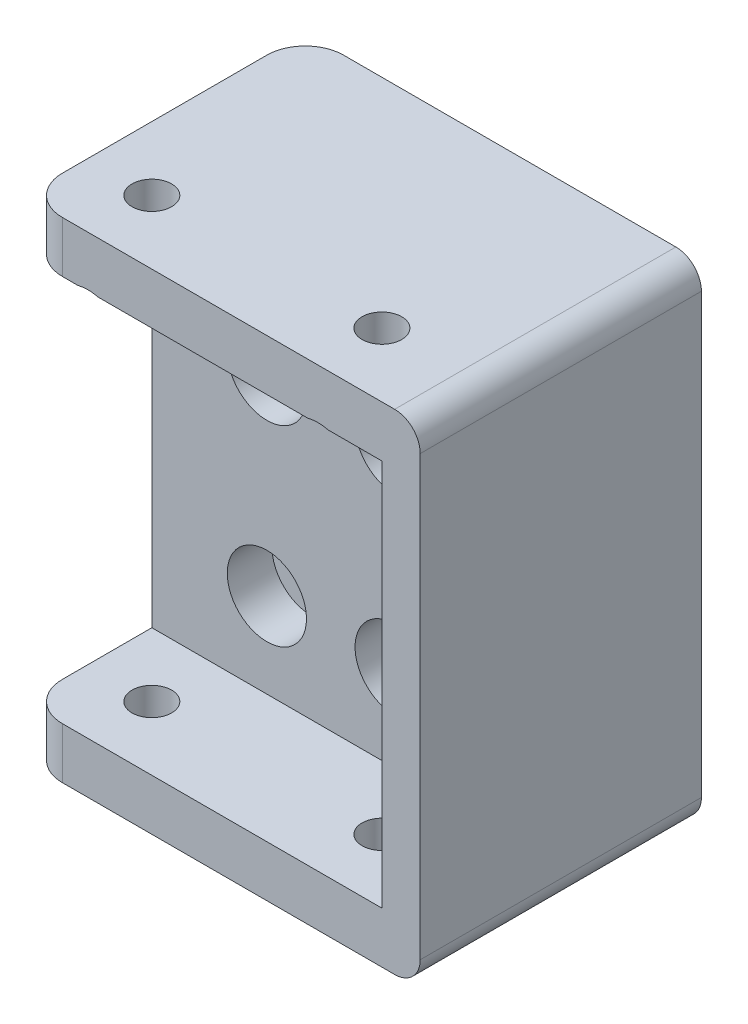
SolidWorks part; units mm, degrees
ref_plane "前视基准面" through (0, 0, 0) normal (0, 0, 1) x (1, 0, 0)
ref_plane "上视基准面" through (0, 0, 0) normal (0, 1, 0) x (1, 0, 0)
ref_plane "右视基准面" through (0, 0, 0) normal (1, 0, 0) x (0, 0, -1)
other "Configuration Table"
sketch "草图1" plane through (0, 0, 0) normal (0, 0, 1) x (1, 0, 0)
  line L1 (-5, 7.5) -> (5, 7.5) construction
  line L2 (-5, 7.5) -> (-5, -7.5) construction
  line L3 (-5, -7.5) -> (5, -7.5) construction
  line L4 (5, 7.5) -> (5, -7.5) construction
  line L5 (-5, 7.5) -> (5, -7.5) construction
  line L6 (-5, -7.5) -> (5, 7.5) construction
  line L7 (-14, 10.15) -> (14, 10.15)
  line L8 (-14, 10.15) -> (-14, -10.15)
  line L9 (-14, -10.15) -> (14, -10.15)
  line L10 (14, 10.15) -> (14, -10.15)
  line L11 (-14, 10.15) -> (14, -10.15) construction
  line L12 (-14, -10.15) -> (14, 10.15) construction
  circle A0 centre (-5, 7.5) radius 1.5
  circle A1 centre (5, 7.5) radius 1.5
  circle A2 centre (5, -7.5) radius 1.5
  circle A3 centre (-5, -7.5) radius 1.5
  point P0 (0, 0)
  point P6 (0, 0)
  dimension "D4" = 3
  dimension "D1" = 15
  dimension "D2" = 10
  dimension "D3" = 28
  dimension "D5" = 20.3
extrude "凸台-拉伸1" add sketch "草图1" along normal blind 5
sketch "草图2" plane through (0, 0, 5) normal (0, 0, 1) x (1, 0, 0)
  line L0 (-14, 0) -> (14, 0)
  line L1 (14, 10.15) -> (-14, 10.15)
  line L2 (-14, -10.15) -> (14, -10.15)
  line L3 (-14, -10.15) -> (-14, -14.15)
  line L4 (14, -10.15) -> (14, 10.15)
  line L5 (14, 10.15) -> (-14, 10.15)
  line L6 (-14, 10.15) -> (-14, -10.15)
  line L7 (-14, -10.15) -> (14, -10.15)
  line L8 (14, -10.15) -> (14, 10.15)
  line L9 (14, 10.15) -> (-14, 10.15)
  line L10 (-14, 10.15) -> (-14, -10.15)
  line L11 (-14, -10.15) -> (14, -10.15)
  line L12 (-14, -14.15) -> (14, -14.15)
  line L13 (14, -10.15) -> (14, -14.15)
  line L14 (14, 10.15) -> (14, 16.15)
  line L15 (-14, 10.15) -> (-14, 16.15)
  line L16 (14, 16.15) -> (-14, 16.15)
  line M11 (14, 10.15) -> (-14, 10.15)
  line M13 (-14, -10.15) -> (14, -10.15)
  dimension "D2" = 4
  dimension "D3" = 6
  dimension "D1" = 0
extrude "凸台-拉伸2" add sketch "草图2" against normal blind 10 contours L14 L16 L15 L1 M11 | L13 L3 L12 M13 region at (0, 13.15, 5) region at (0, -12.15, 5)
sketch "草图3" plane through (0, 0, -5) normal (0, 0, -1) x (-1, 0, 0)
  line L4 (-14, 16.15) -> (-14, 10.15)
  line L5 (-14, 10.15) -> (14, 10.15)
  line L6 (14, 10.15) -> (14, 16.15)
  line L7 (14, 16.15) -> (-14, 16.15)
  line L8 (-14, 16.15) -> (-14, 10.15)
  line L9 (-14, 10.15) -> (14, 10.15)
  line L10 (14, 10.15) -> (14, 16.15)
  line L11 (14, 16.15) -> (-14, 16.15)
  dimension "D1" = 0
extrude "凸台-拉伸3" add sketch "草图3" along normal blind 5
sketch "草图4" plane through (0, 0, 5) normal (0, 0, 1) x (1, 0, 0)
  line L0 (14, 16.15) -> (-14, 16.15) construction
  line L2 (0, 13.15) -> (0, 0) construction
  circle A0 centre (-9, 13.15) radius 1.5
  circle A1 centre (0, 13.15) radius 1.5 construction
  circle A2 centre (9, 13.15) radius 1.5
  dimension "D1" = 3
  dimension "D2" = 3
  dimension "D5" = 9
  dimension "D4" = 3
extrude "切除-拉伸1" cut sketch "草图4" against normal through all
sketch "草图5" plane through (-14, 0, 0) normal (-1, 0, 0) x (0, 0, 1)
  line L0 (0, 16.15) -> (0, -14.15)
  line L8 (0, 10.15) -> (0, -10.15)
  line L9 (0, -10.15) -> (-5, -10.15)
  line L10 (-5, -10.15) -> (-5, -14.15)
  line L11 (-5, -14.15) -> (5, -14.15)
  line L12 (5, -14.15) -> (5, 16.15)
  line L13 (5, 16.15) -> (-10, 16.15)
  line L14 (-10, 16.15) -> (-10, 10.15)
  line L15 (-10, 10.15) -> (0, 10.15)
  line L16 (0, 10.15) -> (0, -10.15)
  line L17 (0, -10.15) -> (-5, -10.15)
  line L18 (-5, -10.15) -> (-5, -14.15)
  line L19 (-5, -14.15) -> (5, -14.15)
  line L20 (5, -14.15) -> (5, 16.15)
  line L21 (5, 16.15) -> (-10, 16.15)
  line L22 (-10, 16.15) -> (-10, 10.15)
  line L23 (-10, 10.15) -> (0, 10.15)
  line M10 (0, -10.15) -> (-5, -10.15)
  line M11 (-5, -10.15) -> (-5, -14.15)
  line M12 (-5, -14.15) -> (5, -14.15)
  line M14 (5, 16.15) -> (-10, 16.15)
  line M15 (-10, 16.15) -> (-10, 10.15)
  line M16 (-10, 10.15) -> (0, 10.15)
  dimension "D1" = 0
extrude "切除-拉伸2" cut sketch "草图5" against normal through all contours L0 M14 M15 M16 | L0 M10 M11 M12 region at (-14, 13.15, -5) region at (-14, -12.15, -2.5)
sketch "草图6" plane through (0, 0, 5) normal (0, 0, 1) x (1, 0, 0)
  line L4 (14, -14.15) -> (14, 16.15)
  line L5 (14, 16.15) -> (-14, 16.15)
  line L6 (-14, 16.15) -> (-14, -14.15)
  line L7 (-14, -14.15) -> (14, -14.15)
  line L8 (14, -14.15) -> (14, 16.15)
  line L9 (14, 16.15) -> (-14, 16.15)
  line L10 (-14, 16.15) -> (-14, -14.15)
  line L11 (-14, -14.15) -> (14, -14.15)
  dimension "D1" = 0
extrude "切除-拉伸3" cut sketch "草图6" against normal blind 1
sketch "草图7" plane through (0, 0, 4) normal (0, 0, 1) x (1, 0, 0)
  line L0 (-14, -14.15) -> (14, -14.15)
  line L1 (-14, -14.15) -> (-14, -18.15)
  line L2 (14, -14.15) -> (14, -18.15)
  line L3 (-14, -18.15) -> (14, -18.15)
  line L4 (-14, -14.15) -> (14, -14.15)
  line L5 (14, -14.15) -> (14, 16.15)
  line L6 (14, 16.15) -> (-14, 16.15)
  line L7 (-14, 16.15) -> (-14, -14.15)
  line L8 (-14, -14.15) -> (14, -14.15)
  line L9 (14, -14.15) -> (14, 16.15)
  line L10 (14, 16.15) -> (-14, 16.15)
  line L11 (-14, 16.15) -> (-14, -14.15)
  line L12 (-14, 16.15) -> (14, 16.15)
  line L13 (-14, 16.15) -> (-14, 20.15)
  line L14 (14, 16.15) -> (14, 20.15)
  line L15 (-14, 20.15) -> (14, 20.15)
  line M11 (-14, -14.15) -> (14, -14.15)
  line M13 (14, 16.15) -> (-14, 16.15)
  dimension "D2" = 4
  dimension "D3" = 4
  dimension "D1" = 0
extrude "凸台-拉伸4" add sketch "草图7" against normal blind 10 and the other way blind 12 contours L15 L13 L14 M13 | L1 L3 L2 M11 region at (0, -16.15, 4) region at (0, 18.15, 4)
sketch "草图9" plane through (0, 0, 4) normal (0, 0, 1) x (1, 0, 0)
  circle A0 centre (5, -7.5) radius 1.5 construction
  circle A1 centre (-5, -7.5) radius 1.5 construction
  circle A2 centre (9, 13.15) radius 1.5 construction
  circle A3 centre (5, 7.5) radius 1.5 construction
  circle A4 centre (-5, 7.5) radius 1.5 construction
  circle A5 centre (-9, 13.15) radius 1.5 construction
  circle A6 centre (5, -7.5) radius 1.5
  circle A7 centre (-5, -7.5) radius 1.5
  circle A8 centre (9, 13.15) radius 1.5
  circle A9 centre (5, 7.5) radius 1.5
  circle A10 centre (-5, 7.5) radius 1.5
  circle A11 centre (-9, 13.15) radius 1.5
  circle A12 centre (-9, 13.15) radius 3.1
  circle A13 centre (-5, 7.5) radius 3.1
  circle A14 centre (5, 7.5) radius 3.1
  circle A15 centre (9, 13.15) radius 3.1
  circle A16 centre (5, -7.5) radius 3.1
  circle A17 centre (-5, -7.5) radius 3.1
  dimension "D1" = 1.6
  dimension "D2" = 1.6
extrude "切除-拉伸4" cut sketch "草图9" against normal blind 1.5 and the other way through all
sketch "草图10" plane through (0, -14.15, 0) normal (0, 1, 0) x (1, 0, 0)
  line L0 (0, -4) -> (0, -16)
  line L4 (14, -4) -> (-14, -4)
  line L5 (-14, -4) -> (-14, -16)
  line L6 (-14, -16) -> (14, -16)
  line L7 (14, -16) -> (14, -4)
  line L8 (14, -4) -> (-14, -4)
  line L9 (-14, -4) -> (-14, -16)
  line L10 (-14, -16) -> (14, -16)
  line L11 (14, -16) -> (14, -4)
  circle A0 centre (-9, -11) radius 1.55
  circle A1 centre (9, -11) radius 1.55
  dimension "D2" = 3.1
  dimension "D3" = 5
  dimension "D4" = 5
  dimension "D1" = 0
extrude "切除-拉伸5" cut sketch "草图10" against normal through all and the other way through all contours A0 | A1 region at (-9, -14.15, 11) region at (9, -14.15, 11)
sketch "草图11" plane through (14, 0, 0) normal (1, 0, 0) x (0, 0, -1)
  line L0 (-16, 16.15) -> (-16, -14.15)
  line L1 (6, 18.4397) -> (6, -14.15)
  line L12 (-4, 16.15) -> (-4, -14.15)
  line L13 (-4, -14.15) -> (-16, -14.15)
  line L14 (-16, -14.15) -> (-16, -18.15)
  line L15 (-16, -18.15) -> (6, -18.15)
  line L16 (6, -18.15) -> (6, -14.15)
  line L17 (6, -14.15) -> (0, -14.15)
  line L18 (0, -14.15) -> (0, 16.15)
  line L19 (0, 16.15) -> (6, 16.15)
  line L20 (6, 16.15) -> (6, 20.15)
  line L21 (6, 20.15) -> (-16, 20.15)
  line L22 (-16, 20.15) -> (-16, 16.15)
  line L23 (-16, 16.15) -> (-4, 16.15)
  line L24 (-4, 16.15) -> (-4, -14.15)
  line L25 (-4, -14.15) -> (-16, -14.15)
  line L26 (-16, -14.15) -> (-16, -18.15)
  line L27 (-16, -18.15) -> (6, -18.15)
  line L28 (6, -18.15) -> (6, -14.15)
  line L29 (6, -14.15) -> (0, -14.15)
  line L30 (0, -14.15) -> (0, 16.15)
  line L31 (0, 16.15) -> (6, 16.15)
  line L32 (6, 16.15) -> (6, 20.15)
  line L33 (6, 20.15) -> (-16, 20.15)
  line L34 (-16, 20.15) -> (-16, 16.15)
  line L38 (-16, 16.15) -> (-4, 16.15)
  line M13 (-4, 16.15) -> (-4, -14.15)
  line M14 (-4, -14.15) -> (-16, -14.15)
  line M15 (-16, -14.15) -> (-16, -18.15)
  line M16 (-16, -18.15) -> (6, -18.15)
  line M17 (6, -18.15) -> (6, -14.15)
  line M18 (6, -14.15) -> (0, -14.15)
  line M19 (0, -14.15) -> (0, 16.15)
  line M20 (0, 16.15) -> (6, 16.15)
  line M21 (6, 16.15) -> (6, 20.15)
  line M22 (6, 20.15) -> (-16, 20.15)
  line M23 (-16, 20.15) -> (-16, 16.15)
  line M24 (-16, 16.15) -> (-4, 16.15)
  dimension "D1" = 0
extrude "凸台-拉伸5" add sketch "草图11" along normal blind 3 contours M24 M13 M14 M15 M16 M17 M18 M19 M20 M21 M22 M23 | L0 M24 M14 M13 | L1 M20 M19 M18 region at (14, 1, 10) region at (14, 1, 3.7766) region at (14, 1, -3)
fillet "圆角1" radius 2 2 edges at (17, -18.15, 5) (17, 20.15, 5)
fillet "圆角2" radius 3 4 edges at (-14, 18.15, 16) (-14, -16.15, 16) (-14, 18.15, -6) (-14, -16.15, -6)
sketch "草图12" plane through (0, 0, 2.5) normal (0, 0, 1) x (1, 0, 0)
  circle A0 centre (-9, 13.15) radius 3.1 construction
  circle A1 centre (9, 13.15) radius 3.1 construction
  circle A2 centre (-9, 13.15) radius 3.1
  circle A3 centre (9, 13.15) radius 3.1
sketch "草图13" plane through (0, 0, 4) normal (0, 0, 1) x (1, 0, 0)
  line L6 (14, 16.15) -> (9.781, 16.15)
  line L7 (8.219, 16.15) -> (-8.219, 16.15)
  line L8 (-9.781, 16.15) -> (-14, 16.15)
  line L9 (-14, 16.15) -> (-14, -14.15)
  line L10 (-14, -14.15) -> (14, -14.15)
  line L11 (14, -14.15) -> (14, 16.15)
  line L12 (14, 16.15) -> (9.781, 16.15)
  line L13 (8.219, 16.15) -> (-8.219, 16.15)
  line L14 (-9.781, 16.15) -> (-14, 16.15)
  line L15 (-14, 16.15) -> (-14, -14.15)
  line L16 (-14, -14.15) -> (14, -14.15)
  line L17 (14, -14.15) -> (14, 16.15)
  circle A1 centre (5, -7.5) radius 3.1
  arc A2 (8.219, 16.15) -> (9.781, 16.15) centre (9, 13.15) ccw
  arc A3 (-9.781, 16.15) -> (-8.219, 16.15) centre (-9, 13.15) ccw
  arc A4 (8.219, 16.15) -> (9.781, 16.15) centre (9, 13.15) ccw
  arc A5 (-9.781, 16.15) -> (-8.219, 16.15) centre (-9, 13.15) ccw
  circle A6 centre (5, -7.5) radius 3.1
  circle A7 centre (-5, -7.5) radius 3.1
  circle A8 centre (-5, -7.5) radius 3.1
  circle A9 centre (5, 7.5) radius 3.1
  circle A10 centre (5, 7.5) radius 3.1
  circle A11 centre (-5, 7.5) radius 3.1
  circle A12 centre (-5, 7.5) radius 3.1
  dimension "D1" = 0
  dimension "D2" = 0
  dimension "D3" = 0
  dimension "D4" = 0
  dimension "D5" = 0
extrude "凸台-拉伸6" add sketch "草图13" along normal blind 2
